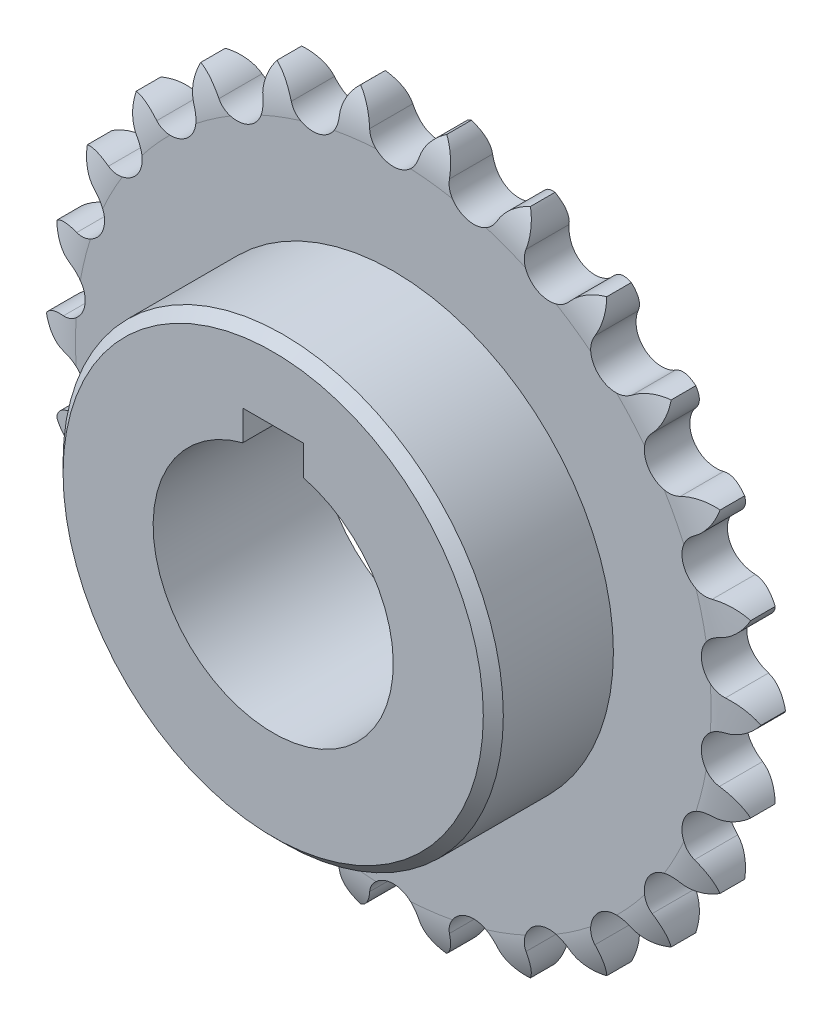
SolidWorks part; units mm, degrees
other "Câmera1"
ref_plane "Plano frontal" through (0, 0, 0) normal (0, 0, 1) x (1, 0, 0)
ref_plane "Plano superior" through (0, 0, 0) normal (0, 1, 0) x (1, 0, 0)
ref_plane "Plano direito" through (0, 0, 0) normal (1, 0, 0) x (0, 0, -1)
sketch "Esboço1" plane through (0, 0, 0) normal (0, 0, 1) x (1, 0, 0)
  line L0 (0, 56.7055) -> (0, 0) construction
  line L1 (0, 0) -> (9.6217, 51.1475) construction
  circle A0 centre (0, 0) radius 19.05
  circle A1 centre (0, 0) radius 52.0446 construction
  circle A2 centre (0, 0) radius 49.2633 construction
  circle A3 centre (0, 0) radius 53.2892 construction
  circle A4 centre (0, 0) radius 56.7055 construction
  arc A5 (3.9297, 52.4145) -> (-3.9297, 52.4145) centre (0, 53.2892) cw
  arc A7 (3.9297, 52.4145) -> (6.8687, 56.288) centre (9.6217, 51.1475) cw
  arc A8 (-3.9297, 52.4145) -> (-6.8687, 56.288) centre (-9.6217, 51.1475) ccw
  arc A9 (16.3591, 49.951) -> (8.7281, 51.8318) centre (12.7529, 51.7407) cw
  arc A10 (8.7281, 51.8318) -> (6.8015, 56.2961) centre (2.8983, 51.9638) ccw
  arc A11 (16.3591, 49.951) -> (20.1397, 53.0086) centre (21.5825, 47.3586) cw
  arc A12 (27.8378, 44.5845) -> (20.8786, 48.2369) centre (24.7647, 47.1852) cw
  arc A13 (20.8786, 48.2369) -> (20.0764, 53.0326) centre (15.2499, 49.7602) ccw
  arc A14 (27.8378, 44.5845) -> (32.2402, 46.6485) centre (32.289, 40.8174) cw
  arc A15 (37.6987, 36.6269) -> (31.8158, 41.8387) centre (35.3373, 39.8875) cw
  arc A16 (31.8158, 41.8387) -> (32.1845, 46.6869) centre (26.7151, 44.6648) ccw
  arc A17 (37.6987, 36.6269) -> (42.4671, 37.5774) centre (41.119, 31.9041) cw
  arc A18 (45.3686, 26.5407) -> (40.9039, 33.0089) centre (43.8562, 30.2717) cw
  arc A19 (40.9039, 33.0089) -> (42.4222, 37.628) centre (36.6278, 36.9736) ccw
  arc A20 (45.3686, 26.5407) -> (50.2259, 26.3224) centre (47.5593, 21.1366) cw
  arc A21 (50.4019, 14.9121) -> (47.6149, 22.2608) centre (49.8263, 18.8966) cw
  arc A22 (47.6149, 22.2608) -> (50.1945, 26.3823) centre (44.4118, 27.1336) ccw
  arc A23 (50.4019, 14.9121) -> (55.0658, 13.5376) centre (51.2356, 9.1407) cw
  arc A24 (52.506, 2.4168) -> (51.5586, 10.2189) centre (52.9007, 6.4233) cw
  arc A25 (51.5586, 10.2189) -> (55.0496, 13.6034) centre (49.6148, 15.7167) ccw
  arc A26 (52.506, 2.4168) -> (56.7055, -0.0338) centre (51.9343, -3.3864) cw
  arc A27 (51.5586, -10.2189) -> (52.506, -2.4168) centre (52.9007, -6.4233) cw
  arc A28 (52.506, -2.4168) -> (56.7055, 0.0338) centre (51.9343, 3.3864) ccw
  arc A29 (51.5586, -10.2189) -> (55.0496, -13.6034) centre (49.6148, -15.7167) cw
  arc A30 (47.6149, -22.2608) -> (50.4019, -14.9121) centre (49.8263, -18.8966) cw
  arc A31 (50.4019, -14.9121) -> (55.0658, -13.5376) centre (51.2356, -9.1407) ccw
  arc A32 (47.6149, -22.2608) -> (50.1945, -26.3823) centre (44.4118, -27.1336) cw
  arc A33 (40.9039, -33.0089) -> (45.3686, -26.5407) centre (43.8562, -30.2717) cw
  arc A34 (45.3686, -26.5407) -> (50.2259, -26.3224) centre (47.5593, -21.1366) ccw
  arc A35 (40.9039, -33.0089) -> (42.4222, -37.628) centre (36.6278, -36.9736) cw
  arc A36 (31.8158, -41.8387) -> (37.6987, -36.6269) centre (35.3373, -39.8875) cw
  arc A37 (37.6987, -36.6269) -> (42.4671, -37.5774) centre (41.119, -31.9041) ccw
  arc A38 (31.8158, -41.8387) -> (32.1845, -46.6869) centre (26.7151, -44.6648) cw
  arc A39 (20.8786, -48.2369) -> (27.8378, -44.5845) centre (24.7647, -47.1852) cw
  arc A40 (27.8378, -44.5845) -> (32.2402, -46.6485) centre (32.289, -40.8174) ccw
  arc A41 (20.8786, -48.2369) -> (20.0764, -53.0326) centre (15.2499, -49.7602) cw
  arc A42 (8.7281, -51.8318) -> (16.3591, -49.951) centre (12.7529, -51.7407) cw
  arc A43 (16.3591, -49.951) -> (20.1397, -53.0086) centre (21.5825, -47.3586) ccw
  arc A44 (8.7281, -51.8318) -> (6.8015, -56.2961) centre (2.8983, -51.9638) cw
  arc A45 (-3.9297, -52.4145) -> (3.9297, -52.4145) centre (0, -53.2892) cw
  arc A46 (3.9297, -52.4145) -> (6.8687, -56.288) centre (9.6217, -51.1475) ccw
  arc A47 (-3.9297, -52.4145) -> (-6.8687, -56.288) centre (-9.6217, -51.1475) cw
  arc A48 (-16.3591, -49.951) -> (-8.7281, -51.8318) centre (-12.7529, -51.7407) cw
  arc A49 (-8.7281, -51.8318) -> (-6.8015, -56.2961) centre (-2.8983, -51.9638) ccw
  arc A50 (-16.3591, -49.951) -> (-20.1397, -53.0086) centre (-21.5825, -47.3586) cw
  arc A51 (-27.8378, -44.5845) -> (-20.8786, -48.2369) centre (-24.7647, -47.1852) cw
  arc A52 (-20.8786, -48.2369) -> (-20.0764, -53.0326) centre (-15.2499, -49.7602) ccw
  arc A53 (-27.8378, -44.5845) -> (-32.2402, -46.6485) centre (-32.289, -40.8174) cw
  arc A54 (-37.6987, -36.6269) -> (-31.8158, -41.8387) centre (-35.3373, -39.8875) cw
  arc A55 (-31.8158, -41.8387) -> (-32.1845, -46.6869) centre (-26.7151, -44.6648) ccw
  arc A56 (-37.6987, -36.6269) -> (-42.4671, -37.5774) centre (-41.119, -31.9041) cw
  arc A57 (-45.3686, -26.5407) -> (-40.9039, -33.0089) centre (-43.8562, -30.2717) cw
  arc A58 (-40.9039, -33.0089) -> (-42.4222, -37.628) centre (-36.6278, -36.9736) ccw
  arc A59 (-45.3686, -26.5407) -> (-50.2259, -26.3224) centre (-47.5593, -21.1366) cw
  arc A60 (-50.4019, -14.9121) -> (-47.6149, -22.2608) centre (-49.8263, -18.8966) cw
  arc A61 (-47.6149, -22.2608) -> (-50.1945, -26.3823) centre (-44.4118, -27.1336) ccw
  arc A62 (-50.4019, -14.9121) -> (-55.0658, -13.5376) centre (-51.2356, -9.1407) cw
  arc A63 (-52.506, -2.4168) -> (-51.5586, -10.2189) centre (-52.9007, -6.4233) cw
  arc A64 (-51.5586, -10.2189) -> (-55.0496, -13.6034) centre (-49.6148, -15.7167) ccw
  arc A65 (-52.506, -2.4168) -> (-56.7055, 0.0338) centre (-51.9343, 3.3864) cw
  arc A66 (-51.5586, 10.2189) -> (-52.506, 2.4168) centre (-52.9007, 6.4233) cw
  arc A67 (-52.506, 2.4168) -> (-56.7055, -0.0338) centre (-51.9343, -3.3864) ccw
  arc A68 (-51.5586, 10.2189) -> (-55.0496, 13.6034) centre (-49.6148, 15.7167) cw
  arc A69 (-47.6149, 22.2608) -> (-50.4019, 14.9121) centre (-49.8263, 18.8966) cw
  arc A70 (-50.4019, 14.9121) -> (-55.0658, 13.5376) centre (-51.2356, 9.1407) ccw
  arc A71 (-47.6149, 22.2608) -> (-50.1945, 26.3823) centre (-44.4118, 27.1336) cw
  arc A72 (-40.9039, 33.0089) -> (-45.3686, 26.5407) centre (-43.8562, 30.2717) cw
  arc A73 (-45.3686, 26.5407) -> (-50.2259, 26.3224) centre (-47.5593, 21.1366) ccw
  arc A74 (-40.9039, 33.0089) -> (-42.4222, 37.628) centre (-36.6278, 36.9736) cw
  arc A75 (-31.8158, 41.8387) -> (-37.6987, 36.6269) centre (-35.3373, 39.8875) cw
  arc A76 (-37.6987, 36.6269) -> (-42.4671, 37.5774) centre (-41.119, 31.9041) ccw
  arc A77 (-31.8158, 41.8387) -> (-32.1845, 46.6869) centre (-26.7151, 44.6648) cw
  arc A78 (-20.8786, 48.2369) -> (-27.8378, 44.5845) centre (-24.7647, 47.1852) cw
  arc A79 (-27.8378, 44.5845) -> (-32.2402, 46.6485) centre (-32.289, 40.8174) ccw
  arc A80 (-20.8786, 48.2369) -> (-20.0764, 53.0326) centre (-15.2499, 49.7602) cw
  arc A81 (-8.7281, 51.8318) -> (-16.3591, 49.951) centre (-12.7529, 51.7407) cw
  arc A82 (-16.3591, 49.951) -> (-20.1397, 53.0086) centre (-21.5825, 47.3586) ccw
  arc A83 (-8.7281, 51.8318) -> (-6.8015, 56.2961) centre (-2.8983, 51.9638) cw
  point P193 (0, 0)
  dimension "D1" = 113.411
  dimension "D2" = 106.5784
  dimension "D3" = 104.0892
  dimension "D4" = 98.5266
  dimension "D5" = 5.8313
  dimension "D6" = 38.1
  dimension "D7" = 26
extrude "Ressalto-extrusão1" add sketch "Esboço1" along normal mid plane 7.213 contours A83 A81 A82 A80 A78 A79 A77 A75 A76 A74 A72 A73 A71 A69 A70 A68 A66 A67 A65 A63 A64 A62 A60 A61 A59 A57 A58 A56 A54 A55 A53 A51 A52 A50 A48 A49 A47 A45 A46 A44 A42 A43 A41 A39 A40 A38 A36 A37 A35 A33 A34 region at (6.2397, 53.6946, 0)
sketch "Esboço2" plane through (0, 0, 0) normal (1, 0, 0) x (0, 0, -1)
  line L0 (-3.6065, 41.8387) -> (-3.6065, 35.8616) construction
  line L5 (-22.6565, 34.925) -> (-3.6065, 34.925)
  line L6 (-22.6565, 34.925) -> (-22.6565, 19.05)
  line L7 (-22.6565, 19.05) -> (-3.6065, 19.05)
  line L8 (-3.6065, 34.925) -> (-3.6065, 19.05)
  line L9 (0, 0) -> (-43.8943, 0) construction
  dimension "D1" = 19.05
  dimension "D2" = 38.1
  dimension "D3" = 69.85
revolve "Revolução1" add sketch "Esboço2" angle 360 about L9
sketch "Esboço3" plane through (0, 0, 22.6565) normal (0, 0, 1) x (1, 0, 0)
  line L0 (0, 0) -> (0, 34.0403) construction
  line L1 (-4.826, 18.4286) -> (4.826, 18.4286)
  line L2 (-4.826, 18.4286) -> (-4.826, 23.1911)
  line L3 (-4.826, 23.1911) -> (4.826, 23.1911)
  line L4 (4.826, 18.4286) -> (4.826, 23.1911)
  circle A0 centre (0, 0) radius 19.05 construction
  dimension "D1" = 9.652
  dimension "D2" = 4.7625
extrude "Corte-extrusão1" cut sketch "Esboço3" against normal through all
sketch "Esboço4" plane through (0, 0, 0) normal (1, 0, 0) x (0, 0, -1)
  line L0 (0, 56.89) -> (0, 43.3023) construction
  line L1 (-1.8343, 56.89) -> (-7.1497, 56.89)
  line L2 (-7.1497, 56.89) -> (-7.1497, 50.419)
  line L3 (-7.1497, 50.419) -> (-3.6065, 50.419)
  line L4 (-3.6065, 52.9981) -> (-3.6065, 48.2369) construction
  line L5 (7.1497, 50.419) -> (3.6065, 50.419)
  line L6 (7.1497, 56.89) -> (7.1497, 50.419)
  line L7 (1.8343, 56.89) -> (7.1497, 56.89)
  line L8 (0, 0) -> (18.1048, 0) construction
  arc A0 (-3.6065, 50.419) -> (-1.8343, 56.89) centre (9.0935, 50.419) cw
  arc A1 (3.6065, 50.419) -> (1.8343, 56.89) centre (-9.0935, 50.419) ccw
  dimension "D3" = 12.7
  dimension "D1" = 50.419
  dimension "D2" = 56.89
revolve "Corte-Revolução1" cut sketch "Esboço4" angle 360 about L8 region at (0, 53.883, 5.0583) region at (0, 53.883, -5.0583)
chamfer "Chanfro1" distance 1.5875 angle 45 1 edges at (-34.925, 0, 22.6565)
ref_axis "Eixo1" through (0, 0, 22.6565) along (0, 0, -1)
